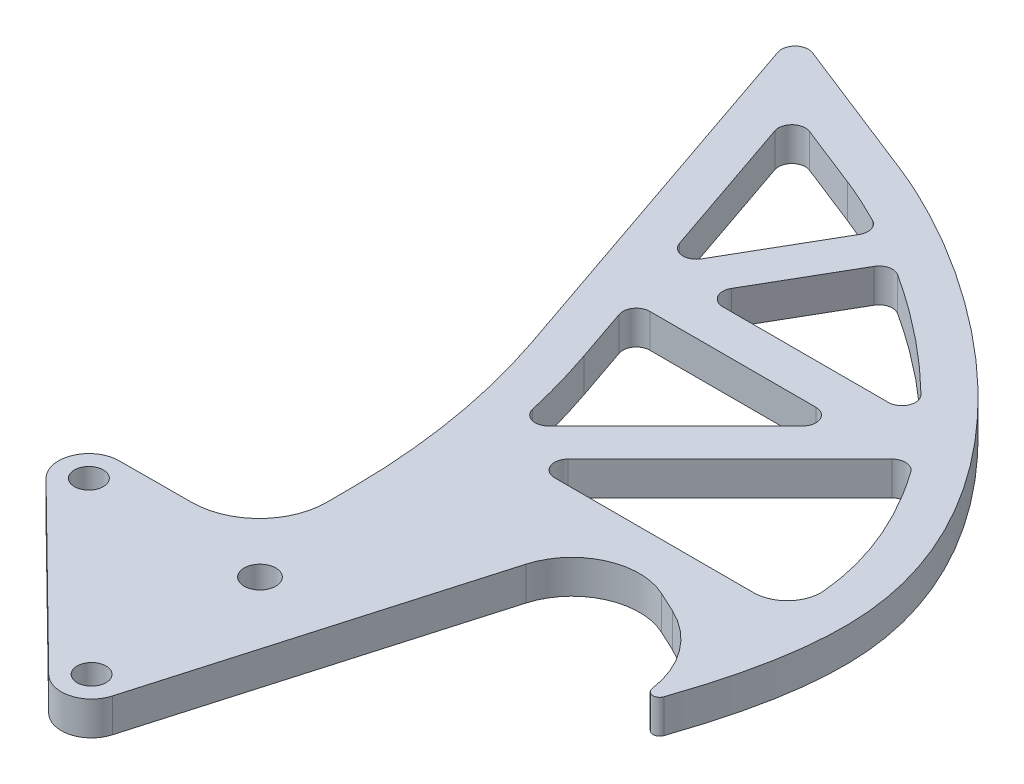
SolidWorks part; units mm, degrees
ref_plane "Front Plane" through (0, 0, 0) normal (0, 0, 1) x (1, 0, 0)
ref_plane "Top Plane" through (0, 0, 0) normal (0, 1, 0) x (1, 0, 0)
ref_plane "Right Plane" through (0, 0, 0) normal (1, 0, 0) x (0, 0, -1)
sketch "Sketch1" plane through (0, 0, 0) normal (0, 1, 0) x (1, 0, 0)
  line L0 (34.9143, 26.2946) -> (21.3197, 32.6339)
  line L1 (21.3197, 32.6339) -> (4.3235, -26.248)
  line L2 (-5, 100) -> (-4.5, -25.018)
  line L3 (-28.5566, -3.2071) -> (-3.1566, -28.2071)
  line L7 (-25.418, 4.5) -> (-4.6184, 4.5832)
  line L13 (0, 0) -> (7.8504, 0) construction
  circle A0 centre (0, 0) radius 2.35
  circle A4 centre (28.575, 12.7) radius 15
  circle A5 centre (0, -25) radius 2.15
  circle A6 centre (0, -25) radius 4.5
  circle A7 centre (-25.4, 0) radius 4.7625 construction
  circle A8 centre (-25.4, 0) radius 2.15
  circle A9 centre (-25.4, 0) radius 4.5
  spline S0 degree 3 poles (42.3892, 6.8546) (44.343, 11.4719) (48.4419, 22.8134) (54.2652, 62.4731) (15.4645, 91.951) (-5, 100) knots 0 0 0 0 0.134758 0.296973 1 1 1 1
  dimension "D2" = 30
  dimension "D9" = 100
  dimension "D6" = 9
  dimension "D17" = 9.525
  dimension "D20" = 4.3
  dimension "D21" = 4.3
  dimension "D22" = 4.7
  dimension "D3" = 28.575
  dimension "D4" = 12.7
  dimension "D5" = 25
  dimension "D7" = 15
  dimension "D8" = 5
  dimension "D10" = 19
  dimension "D11" = 20
  dimension "D12" = 2
  dimension "D13" = 19
  dimension "D14" = 5
  dimension "D15" = 15
  dimension "D16" = 25
  dimension "D18" = 25.4
  dimension "D19" = 13.8142
extrude "Boss-Extrude1" add sketch "Sketch1" along normal blind 5 contours A0 | A6 A5 | A9 L3 A6 L2 L7 | A9 A8 | L1 A4 region at (15.7098, 0, -44.6744) region at (15.5979, 0, -16.4458) region at (1.1079, 0, 29.23) region at (-12.5489, 0, 7.4128) region at (-22.3142, 0, -3.0982)
sketch "Sketch2" plane through (0, 5, 0) normal (0, 1, 0) x (1, 0, 0)
  line L0 (-5, 100) -> (-30.4402, 110.006)
  line L1 (-30.4402, 110.006) -> (-4.74, 35)
  line L2 (-5, 100) -> (-4.6184, 4.5832) construction
  line L3 (-4.74, 35) -> (-5, 100)
  spline S0 degree 3 poles (42.3892, 6.8546) (44.343, 11.4719) (48.4419, 22.8134) (54.2652, 62.4731) (15.4645, 91.951) (-5, 100) knots 0 0 0 0 0.134758 0.296973 1 1 1 1 construction
  dimension "D1" = 25.4
  dimension "D2" = 65
extrude "Boss-Extrude2" add sketch "Sketch2" against normal through all
fillet "Fillet9" radius 1 1 edges at (42.3892, 2.5, -6.8546)
fillet "Fillet10" radius 10 1 edges at (21.3197, 2.5, -32.6339)
fillet "Fillet11" radius 10 1 edges at (-4.6184, 2.5, -4.5832)
fillet "Fillet12" radius 2 1 edges at (-30.4402, 2.5, -110.006)
fillet "Fillet13" radius 100 1 edges at (-4.74, 2.5, -35)
sketch "Sketch3" plane through (0, 5, 0) normal (0, 1, 0) x (1, 0, 0)
  line L0 (-20.5567, 99.6712) -> (-4.3965, 52.5079)
  line L1 (0.0373, 34.6314) -> (31.4993, 66.0935) construction
  line L2 (-14.5943, -1.4568) -> (-21.7525, -1.4854)
  line L3 (31.4993, 66.0935) -> (-9.0515, 66.0935) construction
  line L4 (-9.0515, 66.0935) -> (4.0971, 88.8675) construction
  line L5 (34.448, 33.1323) -> (37.45, 31.7325)
  line L6 (-7.1961, 94.4164) -> (-20.5567, 99.6712)
  line L7 (-5, 100) -> (-26.4137, 108.4223)
  line L8 (-29.0377, 105.9128) -> (-10.0726, 50.5631)
  line L9 (-4.6742, 18.5488) -> (-4.6584, 14.5831)
  line L10 (-14.6183, 4.5432) -> (-25.418, 4.5)
  line L11 (-28.5566, -3.2071) -> (-3.1566, -28.2071)
  line L12 (4.3235, -26.248) -> (18.0784, 21.4047)
  line L13 (31.9123, 27.6945) -> (34.9143, 26.2946)
  line L14 (-5, 100) -> (-26.4137, 108.4223)
  line L15 (-29.0377, 105.9128) -> (-10.0726, 50.5631)
  line L16 (-4.6742, 18.5488) -> (-4.6584, 14.5831)
  line L17 (-14.6183, 4.5432) -> (-25.418, 4.5)
  line L18 (-28.5566, -3.2071) -> (-3.1566, -28.2071)
  line L19 (4.3235, -26.248) -> (18.0784, 21.4047)
  line L20 (31.9123, 27.6945) -> (34.9143, 26.2946)
  line L21 (27.6861, 34.6314) -> (0.0373, 34.6314)
  line L22 (1.48, 90.3346) -> (-10.3417, 69.8588)
  line L23 (-0.7427, -22.1643) -> (12.3137, 23.0686) construction
  line L24 (1.3257, 18.5728) -> (1.3416, 14.6071) construction
  line L25 (-21.7525, -1.4854) -> (-0.7427, -22.1643) construction
  line L26 (6.6705, 87.3248) -> (-3.8554, 69.0935)
  line L27 (-3.8554, 69.0935) -> (28.8919, 69.0935)
  line L28 (-8.0236, 63.0935) -> (24.2567, 63.0935)
  line L29 (24.2567, 63.0935) -> (-0.5952, 38.2416)
  line L30 (4.2799, 34.6314) -> (33.3771, 63.7286)
  line L31 (27.6861, 34.6314) -> (43.6839, 34.6314)
  arc A0 (0.0373, 34.6314) -> (-4.3965, 52.5079) centre (-104.6734, 18.1489) ccw
  arc A2 (-21.7525, -1.4854) -> (-21.7525, -1.4854) centre (-21.7525, -1.4854) ccw
  arc A3 (-0.7427, -22.1643) -> (-0.7427, -22.1643) centre (-0.7427, -22.1643) ccw
  arc A4 (34.448, 33.1323) -> (27.6861, 34.6314) centre (27.6861, 18.6314) ccw
  arc A5 (42.8475, 28.1044) -> (37.45, 31.7325) centre (28.575, 12.7) ccw
  arc A6 (42.8475, 28.1044) -> (42.8475, 28.1044) centre (42.8475, 28.1044) ccw
  arc A7 (-20.5567, 99.6712) -> (-20.5567, 99.6712) centre (-20.5567, 99.6712) ccw
  arc A8 (-26.4137, 108.4223) -> (-29.0377, 105.9128) centre (-27.1457, 106.5611) ccw
  arc A9 (-4.6742, 18.5488) -> (-10.0726, 50.5631) centre (-104.6734, 18.1489) ccw
  arc A10 (-14.6183, 4.5432) -> (-4.6584, 14.5831) centre (-14.6583, 14.5431) ccw
  arc A11 (-25.418, 4.5) -> (-28.5566, -3.2071) centre (-25.4, 0) ccw
  arc A12 (-3.1566, -28.2071) -> (4.3235, -26.248) centre (0, -25) ccw
  arc A13 (31.9123, 27.6945) -> (18.0784, 21.4047) centre (27.6861, 18.6314) ccw
  arc A14 (43.4295, 14.7844) -> (34.9143, 26.2946) centre (28.575, 12.7) ccw
  arc A15 (43.4295, 14.7844) -> (45.3652, 14.5975) centre (44.4198, 14.9234) ccw
  arc A16 (-26.4137, 108.4223) -> (-29.0377, 105.9128) centre (-27.1457, 106.5611) ccw
  arc A17 (-4.6742, 18.5488) -> (-10.0726, 50.5631) centre (-104.6734, 18.1489) ccw
  arc A18 (-14.6183, 4.5432) -> (-4.6584, 14.5831) centre (-14.6583, 14.5431) ccw
  arc A19 (-25.418, 4.5) -> (-28.5566, -3.2071) centre (-25.4, 0) ccw
  arc A20 (-3.1566, -28.2071) -> (4.3235, -26.248) centre (0, -25) ccw
  arc A21 (31.9123, 27.6945) -> (18.0784, 21.4047) centre (27.6861, 18.6314) ccw
  arc A22 (43.4295, 14.7844) -> (34.9143, 26.2946) centre (28.575, 12.7) ccw
  arc A23 (43.4295, 14.7844) -> (45.3652, 14.5975) centre (44.4198, 14.9234) ccw
  arc A24 (1.3257, 18.5728) -> (-4.3965, 52.5079) centre (-104.6734, 18.1489) ccw construction
  arc A25 (34.448, 33.1323) -> (12.3137, 23.0686) centre (27.6861, 18.6314) ccw construction
  arc A26 (-14.5943, -1.4568) -> (1.3416, 14.6071) centre (-14.6583, 14.5431) ccw construction
  spline S0 degree 1 poles (42.8475, 28.1044) (-7.1961, 94.4164) knots 0 0 1 1 construction
  spline S1 degree 3 poles (1217.9881, 1634.3819) (-121.0012, -122.6037) (36.6809, -57.285) (68.1841, 157.2676) (-533.4535, 217.9006) (1742.01, -868.8164) knots -2.019642 -2.019642 -2.019642 -2.019642 0.134758 0.296973 3.3902 3.3902 3.3902 3.3902 only from (45.3652, 14.5975) to (-5, 100)
  spline S2 degree 3 poles (45.3652, 14.5975) (46.1819, 16.9667) (48.8589, 25.6533) (54.2652, 62.4731) (15.4645, 91.951) (-5, 100) knots 0.071607 0.071607 0.071607 0.071607 0.134758 0.296973 1 1 1 1
  spline S3 degree 3 poles (42.8475, 28.1044) (43.0201, 29.0107) (43.314, 30.7711) (43.5388, 32.7131) (43.6597, 34.1916) (43.7678, 36.0249) (43.7686, 39.3312) (43.2118, 43.7559) (41.8173, 48.7829) (39.7143, 53.7786) (37.0327, 58.5832) (34.6353, 62.0784) (33.0755, 64.1269) (32.4544, 64.9171) (31.8233, 65.7036) (31.0811, 66.6011) (30.2703, 67.5479) (29.3429, 68.6019) (26.4297, 71.7961) (22.0093, 76.0293) (16.2406, 80.7525) (11.641, 84.113) (8.2248, 86.364) (6.2322, 87.597) (5.3597, 88.1241) (4.5163, 88.6252) (3.6564, 89.1241) (2.7815, 89.6192) (1.9112, 90.1023) (0.763, 90.7231) (-0.9111, 91.5933) (-2.9262, 92.5797) (-4.7502, 93.4047) (-6.1683, 94.0051) (-6.85, 94.2802) (-7.1961, 94.4164) knots 0.178552 0.178552 0.178552 0.178552 0.204222 0.227791 0.234209 0.247044 0.281233 0.332574 0.383914 0.435255 0.486595 0.533807 0.546745 0.553214 0.559682 0.57262 0.58296 0.591365 0.608173 0.691957 0.743298 0.794638 0.837083 0.85076 0.857808 0.864856 0.877692 0.885406 0.89312 0.905955 0.922989 0.94866 0.97433 0.987165 1 1 1 1
  dimension "D3" = 45
  dimension "D4" = 45
  dimension "D5" = 60
  dimension "D6" = 6
  dimension "D7" = 6
  dimension "D8" = 6
  dimension "D1" = 0
  dimension "D2" = 6
extrude "Cut-Extrude1" cut sketch "Sketch3" against normal blind 10 contours L22 S3 L6 L0 | L27 S3 L26 | A0 L29 L28 L0 | L31 S3 L30 L21 region at (-9.7676, 5, -86.7682) region at (5.4016, 5, -54.9219) region at (11.0171, 5, -75.3642) region at (28.2876, 5, -44.7746)
fillet "Fillet16" radius 2 11 edges at (33.3771, 2.5, -63.7286) (-20.5567, 2.5, -99.6712) (-10.3417, 2.5, -69.8588) (1.48, 2.5, -90.3346) (6.6705, 2.5, -87.3248) (-3.8554, 2.5, -69.0935) (28.8919, 2.5, -69.0935) (-8.0236, 2.5, -63.0935) (-0.5952, 2.5, -38.2416) (24.2567, 2.5, -63.0935) (4.2799, 2.5, -34.6314)
fillet "Fillet17" radius 5 1 edges at (43.6839, 2.5, -34.6314)
